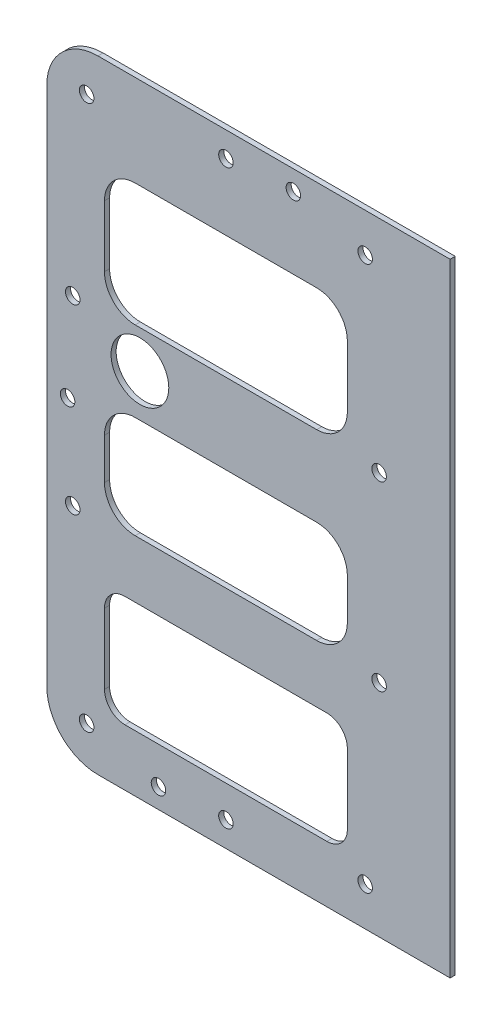
SolidWorks part; units mm, degrees
material "ASTM A36 Steel"
ref_plane "X-Y Datum" through (0, 0, 0) normal (0, 0, 1) x (1, 0, 0)
ref_plane "X-Z Datum" through (0, 0, 0) normal (0, 1, 0) x (1, 0, 0)
ref_plane "Y-Z Datum" through (0, 0, 0) normal (1, 0, 0) x (0, 0, -1)
sketch "Sketch2" plane through (0, 0, -401.5041) normal (0, 0, 1) x (1, 0, 0)
  line L1 (-6.6508, 25.9201) -> (-6.6508, 184.6701) construction
  line L3 (26.1152, 25.9201) -> (-39.4168, 25.9201) construction
  line L4 (-39.4168, 184.6701) -> (26.1152, 184.6701) construction
  line L5 (33.1665, 105.2951) -> (-46.3411, 105.2951) construction
  line L6 (33.1665, 179.3361) -> (33.1665, 31.2541) construction
  line L7 (-46.3411, 179.3361) -> (-46.3411, 31.2541) construction
  line L9 (48.9117, 8.7751) -> (-62.2133, 8.7751)
  line L10 (48.9117, 8.7751) -> (48.9117, 201.8151)
  line L11 (48.9117, 201.8151) -> (-62.2133, 201.8151)
  line L12 (-62.2133, 8.7751) -> (-62.2133, 201.8151)
  line L13 (48.9117, 8.7751) -> (-62.2133, 201.8151) construction
  line L14 (48.9117, 201.8151) -> (-62.2133, 8.7751) construction
  line L30 (29.671, 190.6701) -> (-1.1508, 190.6701)
  line L31 (-1.1508, 190.6701) -> (-1.1508, 194.0798)
  line L32 (-12.1508, 194.0798) -> (-12.1508, 190.6701)
  line L33 (-12.1508, 190.6701) -> (-42.9727, 190.6701)
  line L34 (-42.9727, 190.6701) -> (-45.9531, 193.6505)
  line L35 (-53.7313, 185.8723) -> (-50.7508, 182.8919)
  line L36 (-50.7508, 182.8919) -> (-50.7508, 138.9891)
  line L37 (-50.7508, 138.9891) -> (-54.1605, 138.9891)
  line L38 (-54.1605, 127.9891) -> (-50.7508, 127.9891)
  line L39 (-50.7508, 127.9891) -> (-50.7508, 82.6011)
  line L40 (-50.7508, 82.6011) -> (-54.1605, 82.6011)
  line L41 (-54.1605, 71.6011) -> (-50.7508, 71.6011)
  line L42 (-50.7508, 71.6011) -> (-50.7508, 27.6982)
  line L43 (-50.7508, 27.6982) -> (-53.7313, 24.7178)
  line L44 (-45.9531, 16.9396) -> (-42.9727, 19.9201)
  line L45 (-42.9727, 19.9201) -> (-12.1508, 19.9201)
  line L46 (-12.1508, 19.9201) -> (-12.1508, 16.5104)
  line L47 (-1.1508, 16.5104) -> (-1.1508, 19.9201)
  line L48 (-1.1508, 19.9201) -> (29.671, 19.9201)
  line L49 (29.671, 19.9201) -> (32.6514, 16.9396)
  line L50 (40.4296, 24.7178) -> (37.4492, 27.6982)
  line L51 (37.4492, 27.6982) -> (37.4492, 71.6011)
  line L52 (37.4492, 71.6011) -> (40.8589, 71.6011)
  line L53 (40.8589, 82.6011) -> (37.4492, 82.6011)
  line L54 (37.4492, 82.6011) -> (37.4492, 127.9891)
  line L55 (37.4492, 127.9891) -> (40.8589, 127.9891)
  line L56 (40.8589, 138.9891) -> (37.4492, 138.9891)
  line L57 (37.4492, 138.9891) -> (37.4492, 182.8919)
  line L58 (37.4492, 182.8919) -> (40.4296, 185.8723)
  line L59 (32.6514, 193.6505) -> (29.671, 190.6701)
  line L60 (29.671, 190.6701) -> (-1.1508, 190.6701)
  line L61 (-1.1508, 190.6701) -> (-1.1508, 194.0798)
  line L62 (-12.1508, 194.0798) -> (-12.1508, 190.6701)
  line L63 (-12.1508, 190.6701) -> (-42.9727, 190.6701)
  line L64 (-42.9727, 190.6701) -> (-45.9531, 193.6505)
  line L65 (-53.7313, 185.8723) -> (-50.7508, 182.8919)
  line L66 (-50.7508, 182.8919) -> (-50.7508, 138.9891)
  line L67 (-50.7508, 138.9891) -> (-54.1605, 138.9891)
  line L68 (-54.1605, 127.9891) -> (-50.7508, 127.9891)
  line L69 (-50.7508, 127.9891) -> (-50.7508, 82.6011)
  line L70 (-50.7508, 82.6011) -> (-54.1605, 82.6011)
  line L71 (-54.1605, 71.6011) -> (-50.7508, 71.6011)
  line L72 (-50.7508, 71.6011) -> (-50.7508, 27.6982)
  line L73 (-50.7508, 27.6982) -> (-53.7313, 24.7178)
  line L74 (-45.9531, 16.9396) -> (-42.9727, 19.9201)
  line L75 (-42.9727, 19.9201) -> (-12.1508, 19.9201)
  line L76 (-12.1508, 19.9201) -> (-12.1508, 16.5104)
  line L77 (-1.1508, 16.5104) -> (-1.1508, 19.9201)
  line L78 (-1.1508, 19.9201) -> (29.671, 19.9201)
  line L79 (29.671, 19.9201) -> (32.6514, 16.9396)
  line L80 (40.4296, 24.7178) -> (37.4492, 27.6982)
  line L81 (37.4492, 27.6982) -> (37.4492, 71.6011)
  line L82 (37.4492, 71.6011) -> (40.8589, 71.6011)
  line L83 (40.8589, 82.6011) -> (37.4492, 82.6011)
  line L84 (37.4492, 82.6011) -> (37.4492, 127.9891)
  line L85 (37.4492, 127.9891) -> (40.8589, 127.9891)
  line L86 (40.8589, 138.9891) -> (37.4492, 138.9891)
  line L87 (37.4492, 138.9891) -> (37.4492, 182.8919)
  line L88 (37.4492, 182.8919) -> (40.4296, 185.8723)
  line L89 (32.6514, 193.6505) -> (29.671, 190.6701)
  arc A10 (-1.1508, 194.0798) -> (-12.1508, 194.0798) centre (-6.6508, 194.0798) ccw
  arc A11 (-45.9531, 193.6505) -> (-53.7313, 185.8723) centre (-49.8422, 189.7614) ccw
  arc A12 (-54.1605, 138.9891) -> (-54.1605, 127.9891) centre (-54.1605, 133.4891) ccw
  arc A13 (-54.1605, 82.6011) -> (-54.1605, 71.6011) centre (-54.1605, 77.1011) ccw
  arc A14 (-53.7313, 24.7178) -> (-45.9531, 16.9396) centre (-49.8422, 20.8287) ccw
  arc A15 (-12.1508, 16.5104) -> (-1.1508, 16.5104) centre (-6.6508, 16.5104) ccw
  arc A16 (32.6514, 16.9396) -> (40.4296, 24.7178) centre (36.5405, 20.8287) ccw
  arc A17 (40.8589, 71.6011) -> (40.8589, 82.6011) centre (40.8589, 77.1011) ccw
  arc A18 (40.8589, 127.9891) -> (40.8589, 138.9891) centre (40.8589, 133.4891) ccw
  arc A19 (40.4296, 185.8723) -> (32.6514, 193.6505) centre (36.5405, 189.7614) ccw
  arc A20 (-1.1508, 194.0798) -> (-12.1508, 194.0798) centre (-6.6508, 194.0798) ccw
  arc A21 (-45.9531, 193.6505) -> (-53.7313, 185.8723) centre (-49.8422, 189.7614) ccw
  arc A22 (-54.1605, 138.9891) -> (-54.1605, 127.9891) centre (-54.1605, 133.4891) ccw
  arc A23 (-54.1605, 82.6011) -> (-54.1605, 71.6011) centre (-54.1605, 77.1011) ccw
  arc A24 (-53.7313, 24.7178) -> (-45.9531, 16.9396) centre (-49.8422, 20.8287) ccw
  arc A25 (-12.1508, 16.5104) -> (-1.1508, 16.5104) centre (-6.6508, 16.5104) ccw
  arc A26 (32.6514, 16.9396) -> (40.4296, 24.7178) centre (36.5405, 20.8287) ccw
  arc A27 (40.8589, 71.6011) -> (40.8589, 82.6011) centre (40.8589, 77.1011) ccw
  arc A28 (40.8589, 127.9891) -> (40.8589, 138.9891) centre (40.8589, 133.4891) ccw
  arc A29 (40.4296, 185.8723) -> (32.6514, 193.6505) centre (36.5405, 189.7614) ccw
  point P41 (-6.6508, 105.2951)
  dimension "D2" = 111.125
  dimension "D3" = 193.04
  dimension "D1" = 0
extrude "Boss-Extrude1" add sketch "Sketch2" along normal blind 1.5875 contours L12 L9 L10 L11 A29 L88 L87 L86 A28 L85 L84 L83 A27 L82 L81 L80 A26 L79 L78 L77 A25 L76 L75 L74 A24 L73 L72 L71 A23 L70 L69 L68 A22 L67 L66 L65 A21 L64 L63 L62 A20 L61 L60 L89 | L88 A29 L89 L60 L61 A20 L62 L63 L64 A21 L65 L66 L67 A22 L68 L69 L70 A23 L71 L72 L73 A24 L74 L75 L76 A25 L77 L78 L79 A26 L80 L81 L82 A27 L83 L84 L85 A28 L86 L87 region at (-6.6508, 11.0025, -401.5041) region at (-6.6508, 105.2951, -401.5041)
hole_wizard "M4 Clearance Hole1" positions "Sketch3" profile "Sketch4" hole size "M4" standard "ANSI Metric" end condition through all
sketch "Sketch3" plane through (0, 0, -399.9166) normal (0, 0, 1) x (1, 0, 0)
  point P0 (36.5405, 189.7614)
  point P3 (-6.6508, 194.0798)
  point P6 (-49.8422, 189.7614)
  point P9 (-54.1605, 133.4891)
  point P12 (-54.1605, 77.1011)
  point P15 (-49.8422, 20.8287)
  point P18 (-6.6508, 16.5104)
  point P21 (36.5405, 20.8287)
  point P24 (40.8589, 77.1011)
  point P27 (40.8589, 133.4891)
  point P42 (14.2601, 195.6701)
  point P44 (-55.7508, 105.2951)
  point P46 (-27.5617, 14.9201)
sketch "Sketch4" plane through (36.5405, 189.7614, -399.9166) normal (1, 0, 0) x (0, -1, 0)
  line L0 (0, 0) -> (0, 1.5875)
  line L1 (0, 1.5875) -> (2.25, 1.5875)
  line L2 (2.25, 1.5875) -> (2.25, 0)
  line L5 (2.25, 0) -> (0, 0)
  line L11 (0, -6.35) -> (0, 107.95) construction
  dimension "Thru Hole Dia." = 4.5
  dimension "Thru Hole Depth" = 1.5875
fillet "Fillet1" radius 15.875 2 edges at (-62.2133, 201.8151, -400.7104) (-62.2133, 8.7751, -400.7104)
sketch "Sketch6" plane through (0, 0, -399.9166) normal (0, 0, 1) x (1, 0, 0)
  line L0 (21.2892, 43.3826) -> (-34.5908, 43.3826) construction
  line L3 (-6.6508, 25.9201) -> (-6.6508, 184.6701) construction
  line L4 (-62.2133, 8.7751) -> (48.9117, 8.7751)
  line L5 (48.9117, 8.7751) -> (48.9117, 201.8151)
  line L6 (48.9117, 201.8151) -> (-62.2133, 201.8151)
  line L7 (-62.2133, 201.8151) -> (-62.2133, 8.7751)
  line L8 (-62.2133, 8.7751) -> (48.9117, 8.7751) construction
  line L9 (48.9117, 8.7751) -> (48.9117, 201.8151) construction
  line L10 (48.9117, 201.8151) -> (-62.2133, 201.8151) construction
  line L11 (-62.2133, 201.8151) -> (-62.2133, 8.7751) construction
  line L14 (-6.6508, 25.9201) -> (-6.6508, 60.8451) construction
  line L18 (31.4492, 63.3451) -> (31.4492, 179.3361)
  line L19 (26.1152, 184.6701) -> (-39.4168, 184.6701)
  line L24 (-44.7508, 179.3361) -> (-44.7508, 63.3451)
  line L25 (-44.7508, 63.3451) -> (31.4492, 63.3451)
  line L26 (31.4492, 63.3451) -> (31.4492, 179.3361)
  line L27 (26.1152, 184.6701) -> (-39.4168, 184.6701)
  line L28 (-44.7508, 179.3361) -> (-44.7508, 63.3451)
  line L29 (-44.7508, 63.3451) -> (31.4492, 63.3451)
  line L30 (33.0395, 31.2541) -> (33.0395, 179.3361)
  line L31 (-39.4168, 24.3298) -> (26.1152, 24.3298)
  line L32 (-46.3411, 179.3361) -> (-46.3411, 31.2541)
  line L33 (26.1152, 186.2604) -> (-39.4168, 186.2604)
  line L34 (33.0395, 31.2541) -> (33.0395, 179.3361)
  line L35 (-39.4168, 24.3298) -> (26.1152, 24.3298)
  line L36 (-46.3411, 179.3361) -> (-46.3411, 31.2541)
  line L37 (26.1152, 186.2604) -> (-39.4168, 186.2604)
  line L38 (37.4492, 138.9891) -> (37.4492, 182.8919)
  line L39 (37.4492, 182.8919) -> (40.4296, 185.8723)
  line L40 (32.6514, 193.6505) -> (29.671, 190.6701)
  line L41 (29.671, 190.6701) -> (-1.1508, 190.6701)
  line L42 (-1.1508, 190.6701) -> (-1.1508, 194.0798)
  line L43 (-12.1508, 194.0798) -> (-12.1508, 190.6701)
  line L44 (-12.1508, 190.6701) -> (-42.9727, 190.6701)
  line L45 (-42.9727, 190.6701) -> (-45.9531, 193.6505)
  line L46 (-53.7313, 185.8723) -> (-50.7508, 182.8919)
  line L47 (-50.7508, 182.8919) -> (-50.7508, 138.9891)
  line L48 (-50.7508, 138.9891) -> (-54.1605, 138.9891)
  line L49 (-54.1605, 127.9891) -> (-50.7508, 127.9891)
  line L50 (-50.7508, 127.9891) -> (-50.7508, 82.6011)
  line L51 (-50.7508, 82.6011) -> (-54.1605, 82.6011)
  line L52 (-54.1605, 71.6011) -> (-50.7508, 71.6011)
  line L53 (-50.7508, 71.6011) -> (-50.7508, 27.6982)
  line L54 (-50.7508, 27.6982) -> (-53.7313, 24.7178)
  line L55 (-45.9531, 16.9396) -> (-42.9727, 19.9201)
  line L56 (-42.9727, 19.9201) -> (-12.1508, 19.9201)
  line L57 (-12.1508, 19.9201) -> (-12.1508, 16.5104)
  line L58 (-1.1508, 16.5104) -> (-1.1508, 19.9201)
  line L59 (-1.1508, 19.9201) -> (29.671, 19.9201)
  line L60 (29.671, 19.9201) -> (32.6514, 16.9396)
  line L61 (40.4296, 24.7178) -> (37.4492, 27.6982)
  line L62 (37.4492, 27.6982) -> (37.4492, 71.6011)
  line L63 (37.4492, 71.6011) -> (40.8589, 71.6011)
  line L64 (40.8589, 82.6011) -> (37.4492, 82.6011)
  line L65 (37.4492, 82.6011) -> (37.4492, 127.9891)
  line L66 (37.4492, 127.9891) -> (40.8589, 127.9891)
  line L67 (40.8589, 138.9891) -> (37.4492, 138.9891)
  line L68 (37.4492, 138.9891) -> (37.4492, 182.8919) construction
  line L69 (37.4492, 182.8919) -> (40.4296, 185.8723) construction
  line L70 (32.6514, 193.6505) -> (29.671, 190.6701) construction
  line L71 (29.671, 190.6701) -> (-1.1508, 190.6701) construction
  line L72 (-1.1508, 190.6701) -> (-1.1508, 194.0798) construction
  line L73 (-12.1508, 194.0798) -> (-12.1508, 190.6701) construction
  line L74 (-12.1508, 190.6701) -> (-42.9727, 190.6701) construction
  line L75 (-42.9727, 190.6701) -> (-45.9531, 193.6505) construction
  line L76 (-53.7313, 185.8723) -> (-50.7508, 182.8919) construction
  line L77 (-50.7508, 182.8919) -> (-50.7508, 138.9891) construction
  line L78 (-50.7508, 138.9891) -> (-54.1605, 138.9891) construction
  line L79 (-54.1605, 127.9891) -> (-50.7508, 127.9891) construction
  line L80 (-50.7508, 127.9891) -> (-50.7508, 82.6011) construction
  line L81 (-50.7508, 82.6011) -> (-54.1605, 82.6011) construction
  line L82 (-54.1605, 71.6011) -> (-50.7508, 71.6011) construction
  line L83 (-50.7508, 71.6011) -> (-50.7508, 27.6982) construction
  line L84 (-50.7508, 27.6982) -> (-53.7313, 24.7178) construction
  line L85 (-45.9531, 16.9396) -> (-42.9727, 19.9201) construction
  line L86 (-42.9727, 19.9201) -> (-12.1508, 19.9201) construction
  line L87 (-12.1508, 19.9201) -> (-12.1508, 16.5104) construction
  line L88 (-1.1508, 16.5104) -> (-1.1508, 19.9201) construction
  line L89 (-1.1508, 19.9201) -> (29.671, 19.9201) construction
  line L90 (29.671, 19.9201) -> (32.6514, 16.9396) construction
  line L91 (40.4296, 24.7178) -> (37.4492, 27.6982) construction
  line L92 (37.4492, 27.6982) -> (37.4492, 71.6011) construction
  line L93 (37.4492, 71.6011) -> (40.8589, 71.6011) construction
  line L94 (40.8589, 82.6011) -> (37.4492, 82.6011) construction
  line L95 (37.4492, 82.6011) -> (37.4492, 127.9891) construction
  line L96 (37.4492, 127.9891) -> (40.8589, 127.9891) construction
  line L97 (40.8589, 138.9891) -> (37.4492, 138.9891) construction
  line L98 (31.4492, 31.2541) -> (31.4492, 60.8451)
  line L99 (31.4492, 60.8451) -> (-44.7508, 60.8451)
  line L100 (-44.7508, 60.8451) -> (-44.7508, 31.2541)
  line L101 (-39.4168, 25.9201) -> (26.1152, 25.9201)
  line L102 (31.4492, 31.2541) -> (31.4492, 60.8451)
  line L103 (31.4492, 60.8451) -> (-44.7508, 60.8451)
  line L104 (-44.7508, 60.8451) -> (-44.7508, 31.2541)
  line L105 (-39.4168, 25.9201) -> (26.1152, 25.9201)
  line L152 (3.5092, 43.3826) -> (-16.8108, 43.3826) construction
  circle A0 centre (-34.5908, 43.3826) radius 2.4003
  circle A1 centre (21.2892, 43.3826) radius 2.4003
  circle A2 centre (-20.8847, 82.7899) radius 3
  circle A3 centre (7.5831, 106.4243) radius 3
  arc A4 (31.4492, 179.3361) -> (26.1152, 184.6701) centre (26.1152, 179.3361) ccw
  arc A5 (-39.4168, 184.6701) -> (-44.7508, 179.3361) centre (-39.4168, 179.3361) ccw
  arc A6 (31.4492, 179.3361) -> (26.1152, 184.6701) centre (26.1152, 179.3361) ccw
  arc A7 (-39.4168, 184.6701) -> (-44.7508, 179.3361) centre (-39.4168, 179.3361) ccw
  arc A8 (-44.7508, 31.2541) -> (-39.4168, 25.9201) centre (-39.4168, 31.2541) ccw
  arc A9 (26.1152, 25.9201) -> (31.4492, 31.2541) centre (26.1152, 31.2541) ccw
  arc A10 (40.4296, 185.8723) -> (32.6514, 193.6505) centre (36.5405, 189.7614) ccw
  arc A11 (-1.1508, 194.0798) -> (-12.1508, 194.0798) centre (-6.6508, 194.0798) ccw
  arc A12 (-45.9531, 193.6505) -> (-53.7313, 185.8723) centre (-49.8422, 189.7614) ccw
  arc A13 (-54.1605, 138.9891) -> (-54.1605, 127.9891) centre (-54.1605, 133.4891) ccw
  arc A14 (-54.1605, 82.6011) -> (-54.1605, 71.6011) centre (-54.1605, 77.1011) ccw
  arc A15 (-53.7313, 24.7178) -> (-45.9531, 16.9396) centre (-49.8422, 20.8287) ccw
  arc A16 (-12.1508, 16.5104) -> (-1.1508, 16.5104) centre (-6.6508, 16.5104) ccw
  arc A17 (32.6514, 16.9396) -> (40.4296, 24.7178) centre (36.5405, 20.8287) ccw
  arc A18 (40.8589, 71.6011) -> (40.8589, 82.6011) centre (40.8589, 77.1011) ccw
  arc A19 (40.8589, 127.9891) -> (40.8589, 138.9891) centre (40.8589, 133.4891) ccw
  arc A20 (40.4296, 185.8723) -> (32.6514, 193.6505) centre (36.5405, 189.7614) ccw construction
  arc A21 (-1.1508, 194.0798) -> (-12.1508, 194.0798) centre (-6.6508, 194.0798) ccw construction
  arc A22 (-45.9531, 193.6505) -> (-53.7313, 185.8723) centre (-49.8422, 189.7614) ccw construction
  arc A23 (-54.1605, 138.9891) -> (-54.1605, 127.9891) centre (-54.1605, 133.4891) ccw construction
  arc A24 (-54.1605, 82.6011) -> (-54.1605, 71.6011) centre (-54.1605, 77.1011) ccw construction
  arc A25 (-53.7313, 24.7178) -> (-45.9531, 16.9396) centre (-49.8422, 20.8287) ccw construction
  arc A26 (-12.1508, 16.5104) -> (-1.1508, 16.5104) centre (-6.6508, 16.5104) ccw construction
  arc A27 (32.6514, 16.9396) -> (40.4296, 24.7178) centre (36.5405, 20.8287) ccw construction
  arc A28 (40.8589, 71.6011) -> (40.8589, 82.6011) centre (40.8589, 77.1011) ccw construction
  arc A29 (40.8589, 127.9891) -> (40.8589, 138.9891) centre (40.8589, 133.4891) ccw construction
  arc A30 (26.1152, 24.3298) -> (33.0395, 31.2541) centre (26.1152, 31.2541) ccw
  arc A31 (-46.3411, 31.2541) -> (-39.4168, 24.3298) centre (-39.4168, 31.2541) ccw
  arc A32 (-39.4168, 186.2604) -> (-46.3411, 179.3361) centre (-39.4168, 179.3361) ccw
  arc A33 (33.0395, 179.3361) -> (26.1152, 186.2604) centre (26.1152, 179.3361) ccw
  arc A34 (26.1152, 24.3298) -> (33.0395, 31.2541) centre (26.1152, 31.2541) ccw
  arc A35 (-46.3411, 31.2541) -> (-39.4168, 24.3298) centre (-39.4168, 31.2541) ccw
  arc A36 (-39.4168, 186.2604) -> (-46.3411, 179.3361) centre (-39.4168, 179.3361) ccw
  arc A37 (33.0395, 179.3361) -> (26.1152, 186.2604) centre (26.1152, 179.3361) ccw
  arc A38 (-44.7508, 31.2541) -> (-39.4168, 25.9201) centre (-39.4168, 31.2541) ccw
  arc A39 (26.1152, 25.9201) -> (31.4492, 31.2541) centre (26.1152, 31.2541) ccw
  circle A40 centre (-20.8847, 142.5908) radius 3
  circle A41 centre (7.5831, 166.2252) radius 3
  circle A44 centre (-20.8847, 142.5908) radius 4.675
  circle A46 centre (7.5831, 166.2252) radius 4.675
  circle A48 centre (-20.8847, 82.7899) radius 4.675
  circle A50 centre (7.5831, 106.4243) radius 4.675
  circle A71 centre (3.5092, 43.3826) radius 6.477
  circle A72 centre (-16.8108, 43.3826) radius 6.477
  circle A169 centre (-33.3208, 123.6701) radius 6.477
  circle A573 centre (-6.6508, 94.6071) radius 10 construction
  circle A574 centre (-6.6508, 154.408) radius 10 construction
  circle A607 centre (-6.6508, 154.408) radius 10.762
  circle A608 centre (-6.6508, 94.6071) radius 10.762
  point P29 (-6.6508, 43.3826)
  point P90 (-6.6508, 43.3826)
  point P96 (-6.6508, 43.3826)
  point P99 (7.5831, 166.2252)
  point P100 (-20.8847, 142.5908)
  point P101 (7.5831, 106.4243)
  point P102 (-20.8847, 82.7899)
  dimension "D7" = 4.8006
  dimension "D9" = 12.954
  dimension "D11" = 20
  dimension "D13" = 6
  dimension "D3" = 55.88
  dimension "D8" = 20.32
  dimension "D10" = 11.43
  dimension "2" = 60.325
  dimension "D12" = 0.762
  dimension "D1" = 0
  dimension "D2" = 0
  dimension "D4" = 0
  dimension "D5" = 0
  dimension "D6" = 0
extrude "Cut-Extrude1" cut sketch "Sketch6" against normal through all contours A71 | A1 | A72 | A0 | A169 | A40 | A41 | A608 | A607 region at (-34.5908, 43.3826, -399.9166) region at (21.2892, 43.3826, -399.9166) region at (-20.8847, 142.5908, -399.9166) region at (7.5831, 166.2252, -399.9166) region at (3.5092, 43.3826, -399.9166) region at (-16.8108, 43.3826, -399.9166) region at (-33.3208, 123.6701, -399.9166) region at (-6.6508, 154.408, -399.9166) region at (-6.6508, 94.6071, -399.9166)
sketch "Sketch7" plane through (0, 0, -399.9166) normal (0, 0, 1) x (1, 0, 0)
  line L0 (48.9117, 201.8151) -> (-46.3383, 201.8151) construction
  line L1 (48.9117, 201.8151) -> (62.8817, 201.8151)
  line L2 (48.9117, 201.8151) -> (48.9117, 8.7751)
  line L3 (48.9117, 8.7751) -> (62.8817, 8.7751)
  line L4 (62.8817, 201.8151) -> (62.8817, 8.7751)
  line L5 (48.9117, 8.7751) -> (-46.3383, 8.7751) construction
  dimension "D1" = 13.97
extrude "Boss-Extrude2" add sketch "Sketch7" against normal blind 1.5875
sketch "Sketch8" plane through (0, 0, -399.9166) normal (0, 0, 1) x (1, 0, 0)
  line L0 (31.0114, 173.458) -> (-44.3131, 173.458)
  line L1 (31.0114, 26.3578) -> (-44.3131, 26.3578)
  line L2 (31.0114, 26.3578) -> (31.0114, 184.2323)
  line L3 (31.0114, 184.2323) -> (-44.3131, 184.2323)
  line L4 (-44.3131, 26.3578) -> (-44.3131, 184.2323)
  line L5 (31.0114, 26.3578) -> (-44.3131, 184.2323) construction
  line L6 (31.0114, 184.2323) -> (-44.3131, 26.3578) construction
  line L7 (31.0114, 135.358) -> (-44.3131, 135.358)
  line L8 (31.0114, 78.7321) -> (-44.3131, 78.7321)
  line L10 (31.0114, 123.6701) -> (-44.3131, 123.6701) construction
  line L11 (-44.3131, 60.8451) -> (31.0114, 60.8451)
  line L12 (31.0114, 110.4821) -> (-44.3131, 110.4821)
  line L13 (31.0114, 154.408) -> (-44.3131, 154.408)
  line L14 (31.0114, 94.6071) -> (-44.3131, 94.6071)
  circle A0 centre (-33.3208, 123.6701) radius 8.9535
  circle A1 centre (-33.3208, 123.6701) radius 7.366 construction
  point P0 (-6.6508, 105.2951)
  point P22 (-133.0715, 19.9201)
  point P23 (-133.0715, 19.9201)
  point P27 (-133.0715, 19.9201)
  circle M1 centre (7.5831, 166.2252) radius 3
  circle M3 centre (-20.8847, 142.5908) radius 3
  circle M5 centre (-33.3208, 123.6701) radius 6.477
  circle M6 centre (-34.5908, 43.3826) radius 2.4003
  circle M7 centre (-16.8108, 43.3826) radius 6.477
  circle M8 centre (21.2892, 43.3826) radius 2.4003
  circle M9 centre (-6.6508, 94.6071) radius 10.762
  circle M10 centre (-6.6508, 154.408) radius 10.762
  circle M11 centre (3.5092, 43.3826) radius 6.477
  dimension "D2" = 19.05
  dimension "D3" = 19.05
  dimension "D4" = 15.875
  dimension "D1" = 1.5875
  dimension "D5" = 15.875
extrude "Cut-Extrude2" cut sketch "Sketch8" against normal blind 1.5875 contours L2 L4 L1 M6 M8 M11 M7 | L2 L4 M3 M9 | L2 L3 L4 M10 M1 | A0 M5 | L14 L2 L12 L4 M9 M3 | L2 L13 L4 L7 M10 M1 region at (30.2344, 163.933, -399.9166) region at (30.2344, 144.883, -399.9166) region at (30.2416, 102.5446, -399.9166) region at (30.2416, 86.6696, -399.9166) region at (-6.6508, 43.63, -399.9166) region at (-42.0211, 123.6701, -399.9166)
fillet "Fillet2" radius 9.525 4 edges at (-44.3131, 173.458, -400.7104) (-44.3131, 135.358, -400.7104) (31.0114, 135.358, -400.7104) (31.0114, 173.458, -400.7104)
fillet "Fillet3" radius 6.35 4 edges at (-44.3131, 26.3578, -400.7104) (31.0114, 26.3578, -400.7104) (31.0114, 60.8451, -400.7104) (-44.3131, 60.8451, -400.7104)
fillet "Fillet4" radius 9.525 4 edges at (-44.3131, 110.4821, -400.7104) (-44.3131, 78.7321, -400.7104) (31.0114, 78.7321, -400.7104) (31.0114, 110.4821, -400.7104)
